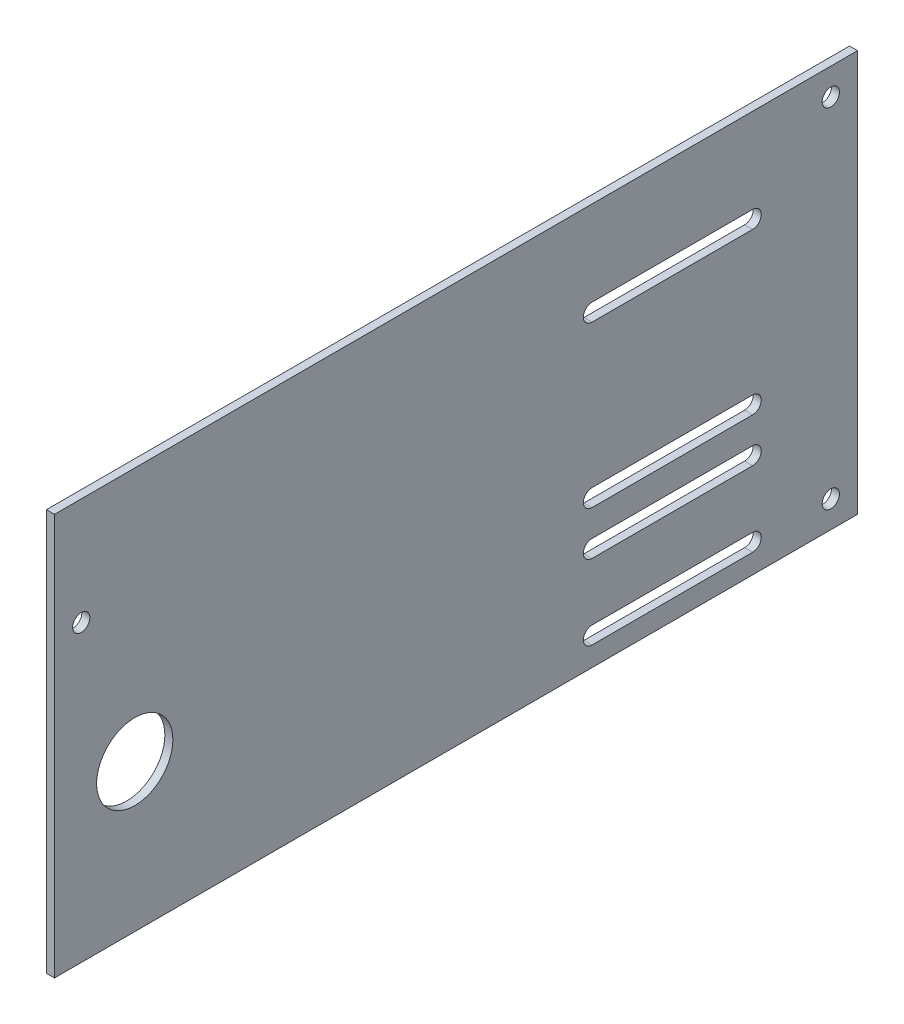
SolidWorks part; units mm, degrees
ref_plane "Front Plane" through (0, 0, 0) normal (0, 0, 1) x (1, 0, 0)
ref_plane "Top Plane" through (0, 0, 0) normal (0, 1, 0) x (1, 0, 0)
ref_plane "Right Plane" through (0, 0, 0) normal (1, 0, 0) x (0, 0, -1)
sketch "Sketch1" plane through (0, 0, 0) normal (1, 0, 0) x (0, 0, -1)
  line L1 (0, 0) -> (300, 0)
  line L2 (0, 0) -> (0, 150)
  line L3 (0, 150) -> (300, 150)
  line L4 (300, 0) -> (300, 150)
  circle A0 centre (30, 55) radius 14.235
  dimension "D1" = 300
  dimension "D5" = 28.47
  dimension "D4" = 55
  dimension "D2" = 150
  dimension "D3" = 30
extrude "Boss-Extrude1" add sketch "Sketch1" along normal blind 3
sketch "Sketch2" plane through (0, 0, 0) normal (-1, 0, 0) x (0, 0, 1)
  line L0 (-260.8, 55) -> (-200.8, 55) construction
  line L1 (-260.8, 58.225) -> (-200.8, 58.225)
  line L2 (-260.8, 51.775) -> (-200.8, 51.775)
  line L3 (-200.8, 115) -> (-260.8, 115) construction
  line L4 (-200.8, 111.77) -> (-260.8, 111.77)
  line L5 (-200.8, 118.23) -> (-260.8, 118.23)
  line L6 (-260.8, 38.55) -> (-200.8, 38.55) construction
  line L9 (-260.8, 41.775) -> (-200.8, 41.775)
  line L10 (-260.8, 35.325) -> (-200.8, 35.325)
  line L11 (-260.8, 10.55) -> (-200.8, 10.55) construction
  line L12 (-260.8, 13.775) -> (-200.8, 13.775)
  line L13 (-260.8, 7.325) -> (-200.8, 7.325)
  line L14 (0, 0) -> (-300, 0) construction
  line L15 (-300, 150) -> (0, 150) construction
  line L16 (-300, 0) -> (-300, 150) construction
  line L17 (0, 150) -> (0, 0) construction
  arc A0 (-260.8, 58.225) -> (-260.8, 51.775) centre (-260.8, 55) ccw
  arc A1 (-200.8, 51.775) -> (-200.8, 58.225) centre (-200.8, 55) ccw
  circle A2 centre (-30, 55) radius 14.235 construction
  arc A3 (-200.8, 111.77) -> (-200.8, 118.23) centre (-200.8, 115) ccw
  arc A4 (-260.8, 118.23) -> (-260.8, 111.77) centre (-260.8, 115) ccw
  arc A7 (-260.8, 41.775) -> (-260.8, 35.325) centre (-260.8, 38.55) ccw
  arc A8 (-200.8, 35.325) -> (-200.8, 41.775) centre (-200.8, 38.55) ccw
  arc A9 (-260.8, 13.775) -> (-260.8, 7.325) centre (-260.8, 10.55) ccw
  arc A10 (-200.8, 7.325) -> (-200.8, 13.775) centre (-200.8, 10.55) ccw
  circle A11 centre (-290, 140) radius 3.225
  circle A12 centre (-10, 110) radius 3.225
  circle A13 centre (-290, 10) radius 3.225
  point P2 (-230.8, 55)
  point P9 (-230.8, 115)
  point P22 (-230.8, 38.55)
  point P34 (-230.8, 10.55)
  dimension "D1" = 3.225
  dimension "D4" = 3.225
  dimension "D6" = 60
  dimension "D8" = 3.225
  dimension "D13" = 6.45
  dimension "D14" = 6.45
  dimension "D15" = 6.45
  dimension "D2" = 200.8
  dimension "D3" = 60
  dimension "D5" = 60
  dimension "D7" = 10
  dimension "D9" = 60
  dimension "D10" = 60
  dimension "D11" = 28
  dimension "D12" = 55
  dimension "D16" = 10
  dimension "D17" = 10
  dimension "D18" = 10
  dimension "D19" = 10
  dimension "D20" = 10
  dimension "D21" = 110
extrude "Cut-Extrude1" cut sketch "Sketch2" against normal up to next
